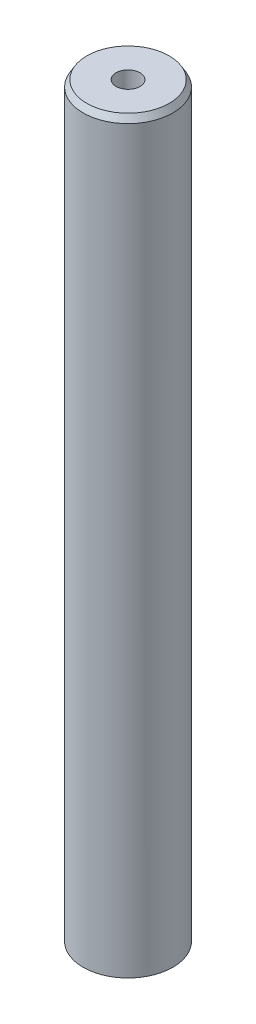
SolidWorks part; units mm, degrees
ref_plane "Front Plane" through (0, 0, 0) normal (0, 0, 1) x (1, 0, 0)
ref_plane "Top Plane" through (0, 0, 0) normal (0, 1, 0) x (1, 0, 0)
ref_plane "Right Plane" through (0, 0, 0) normal (1, 0, 0) x (0, 0, -1)
sketch "Sketch1" plane through (0, 0, 0) normal (0, 1, 0) x (1, 0, 0)
  circle A0 centre (0, 0) radius 10
  dimension "SHAFT_OD" = 20
extrude "Boss-Extrude1" add sketch "Sketch1" along normal blind 167.0744
sketch "Sketch2" plane through (0, 0, 0) normal (0, 1, 0) x (1, 0, 0)
  circle A0 centre (0, 0) radius 2.6605
  dimension "BORE_D" = 5.321
extrude "Cut-Extrude1" cut sketch "Sketch2" along normal through all
chamfer "Chamfer1" distance 1.4278 angle 30 2 edges at (0, 167.0744, 10) (0, 0, 10) first distance on face at (0, 167.0744, 10) first distance on face at (0, 0, 2.6605)
